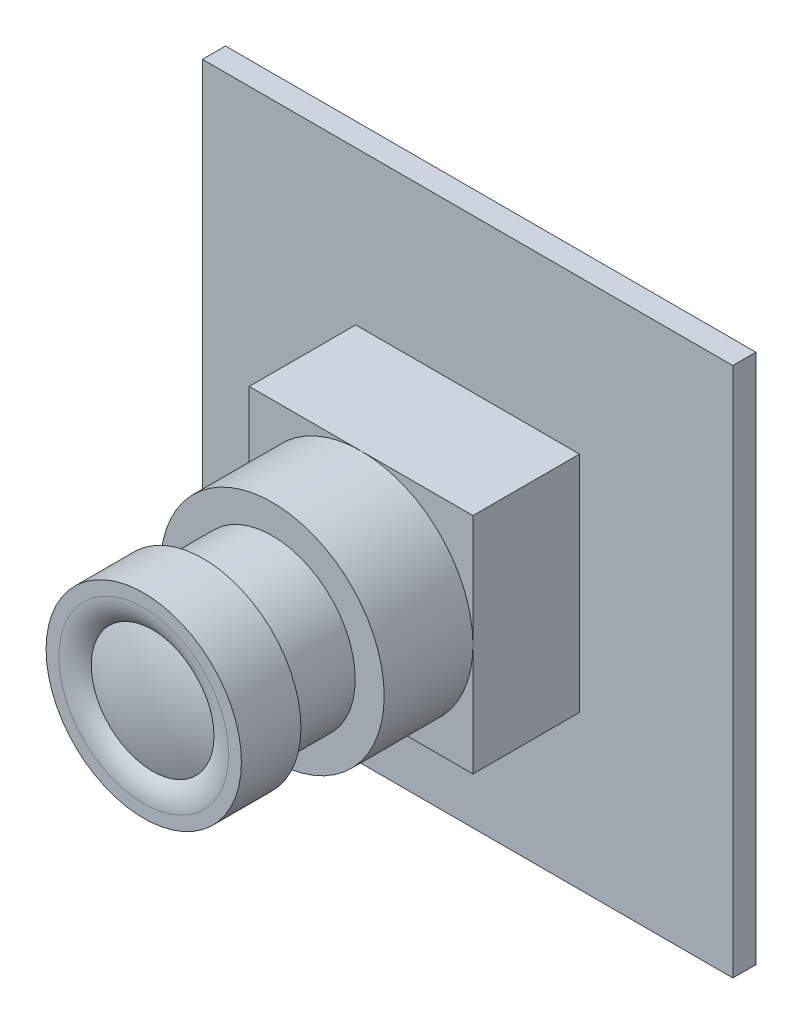
SolidWorks part; units mm, degrees
ref_plane "Front Plane" through (0, 0, 0) normal (0, 0, 1) x (1, 0, 0)
ref_plane "Top Plane" through (0, 0, 0) normal (0, 1, 0) x (1, 0, 0)
ref_plane "Right Plane" through (0, 0, 0) normal (1, 0, 0) x (0, 0, -1)
sketch "Sketch1" plane through (0, 0, 0) normal (0, 0, 1) x (1, 0, 0)
  line L1 (0, 37.9349) -> (37.9349, 37.9349)
  line L2 (0, 37.9349) -> (0, 0)
  line L3 (0, 0) -> (37.9349, 0)
  line L4 (37.9349, 37.9349) -> (37.9349, 0)
  dimension "D1" = 37.9349
extrude "Boss-Extrude1" add sketch "Sketch1" along normal blind 1.651
sketch "Sketch2" plane through (0, 0, 1.651) normal (0, 0, 1) x (1, 0, 0)
  line L0 (37.9349, 18.9675) -> (26.9685, 18.9675) construction
  line L1 (10.9665, 26.9685) -> (26.9684, 26.9685)
  line L2 (10.9665, 26.9685) -> (10.9665, 10.9665)
  line L3 (10.9665, 10.9665) -> (26.9685, 10.9665)
  line L4 (26.9684, 26.9685) -> (26.9685, 10.9665)
  line L5 (0, 0) -> (37.9349, 0) construction
  line L6 (37.9349, 0) -> (37.9349, 37.9349) construction
  line L7 (18.9674, 37.9349) -> (18.9675, 26.9685) construction
  line L10 (37.9349, 37.9349) -> (0, 37.9349) construction
  dimension "D1" = 16.002
extrude "Boss-Extrude2" add sketch "Sketch2" along normal blind 7.62
sketch "Sketch3" plane through (0, 0, 9.271) normal (0, 0, 1) x (1, 0, 0)
  line L1 (26.9684, 26.9685) -> (10.9665, 26.9685) construction
  line L2 (26.9685, 10.9665) -> (26.9684, 26.9685) construction
  line L3 (10.9665, 26.9685) -> (10.9665, 10.9665) construction
  line L4 (10.9665, 10.9665) -> (26.9685, 10.9665) construction
  circle A0 centre (18.9675, 18.9675) radius 8.001
extrude "Boss-Extrude3" add sketch "Sketch3" along normal blind 6.35
sketch "Sketch4" plane through (0, 0, 15.621) normal (0, 0, 1) x (1, 0, 0)
  circle A0 centre (18.9675, 18.9675) radius 5.9309
  circle A1 centre (18.9675, 18.9675) radius 8.001 construction
  dimension "D1" = 11.8618
extrude "Boss-Extrude4" add sketch "Sketch4" along normal blind 4.9403
sketch "Sketch5" plane through (0, 0, 20.5613) normal (0, 0, 1) x (1, 0, 0)
  circle A0 centre (18.9675, 18.9675) radius 6.985
  circle A1 centre (18.9675, 18.9675) radius 5.9309 construction
  dimension "D1" = 13.97
extrude "Boss-Extrude5" add sketch "Sketch5" along normal blind 4.2545
sketch "Sketch6" plane through (0, 0, 24.8158) normal (0, 0, 1) x (1, 0, 0)
  circle A0 centre (18.9675, 18.9675) radius 4.3878
  circle A1 centre (18.9675, 18.9675) radius 6.985 construction
  dimension "D1" = 8.7757
extrude "Cut-Extrude1" cut sketch "Sketch6" against normal blind 0.635
fillet "Fillet2" radius 2.54 1 edges at (23.3553, 18.9675, 24.8158)
dome "Dome1" faces to dome 1 distance 0.762 reverse direction no elliptical dome no face at (23.3553, 18.9675, 24.1808) parameters "D1"=0.762
sketch "Sketch9" plane through (0, 0, 1.651) normal (0, 0, 1) x (1, 0, 0)
  line L0 (32.8168, 32.8168) -> (37.9349, 32.8168) construction
  line L1 (0, 0) -> (37.9349, 0) construction
  line L2 (37.9349, 0) -> (37.9349, 37.9349) construction
  line L3 (32.8168, 37.9349) -> (32.8168, 32.8168) construction
  line L4 (0, 37.9349) -> (0, 0) construction
  line L5 (37.9349, 37.9349) -> (0, 37.9349) construction
  line L6 (5.1181, 37.9349) -> (5.1181, 32.8168) construction
  line L7 (0, 32.8168) -> (5.1181, 32.8168) construction
  line L8 (5.1181, 0) -> (5.1181, 5.1181) construction
  line L9 (0, 5.1181) -> (5.1181, 5.1181) construction
  line L10 (37.9349, 5.1181) -> (32.8168, 5.1181) construction
  line L11 (32.8168, 0) -> (32.8168, 5.1181) construction
  line L12 (18.9674, 37.9349) -> (18.9674, 36.1569) construction
  line L13 (15.508, 36.1569) -> (22.4269, 36.1569)
  line L14 (22.4269, 35.0692) -> (23.5146, 35.0692) construction
  line L15 (15.508, 33.9815) -> (22.4269, 33.9815)
  line L16 (15.508, 35.0692) -> (22.4269, 35.0692) construction
  line L17 (18.9674, 33.9815) -> (18.9675, 26.9685) construction
  line L18 (26.9684, 26.9685) -> (10.9665, 26.9685) construction
  line L19 (14.4203, 35.0692) -> (15.508, 35.0692) construction
  line L20 (15.375, 3.9534) -> (22.5599, 3.9534)
  line L21 (22.4269, 2.8739) -> (23.5146, 2.8739) construction
  line L22 (15.375, 1.7943) -> (22.5599, 1.7943)
  line L23 (15.508, 2.8739) -> (22.4269, 2.8739) construction
  line L24 (14.4203, 2.8739) -> (15.508, 2.8739) construction
  line L25 (33.9815, 22.5599) -> (33.9815, 15.375)
  line L26 (18.9675, 10.9665) -> (18.9675, 3.9534) construction
  line L27 (18.9675, 3.9534) -> (18.9674, 1.7943) construction
  line L28 (36.1394, 22.5599) -> (36.1394, 15.375)
  line L29 (10.9665, 10.9665) -> (26.9685, 10.9665) construction
  line L30 (18.9674, 1.7943) -> (18.9674, 0) construction
  line L31 (18.9674, 36.1569) -> (18.9674, 33.9815) construction
  line L32 (33.9815, 15.375) -> (36.1394, 15.375) construction
  line L33 (35.0604, 22.4269) -> (35.0604, 15.508) construction
  line L34 (35.0604, 23.5141) -> (35.0604, 22.4269) construction
  line L35 (35.0604, 15.508) -> (35.0604, 14.4209) construction
  line L36 (26.9685, 18.9675) -> (33.9815, 18.9675) construction
  line L37 (26.9685, 10.9665) -> (26.9684, 26.9685) construction
  line L38 (1.7955, 22.5599) -> (1.7955, 15.375)
  line L39 (3.9534, 22.5599) -> (3.9534, 15.375)
  line L40 (1.7955, 15.375) -> (3.9534, 15.375) construction
  line L41 (2.8745, 22.4269) -> (2.8745, 15.508) construction
  line L42 (2.8745, 23.5141) -> (2.8745, 22.4269) construction
  line L43 (2.8745, 15.508) -> (2.8745, 14.4209) construction
  line L44 (3.9534, 18.9675) -> (10.9665, 18.9675) construction
  line L45 (10.9665, 26.9685) -> (10.9665, 10.9665) construction
  line L46 (0, 18.9674) -> (1.7955, 18.9675) construction
  circle A0 centre (32.8168, 32.8168) radius 1.1176
  circle A1 centre (5.1181, 32.8168) radius 1.1176
  circle A2 centre (5.1181, 5.1181) radius 1.1176
  circle A3 centre (32.8168, 5.1181) radius 1.1176
  arc A4 (22.4269, 36.1569) -> (22.4269, 33.9815) centre (22.4269, 35.0692) cw
  arc A5 (15.508, 36.1569) -> (15.508, 33.9815) centre (15.508, 35.0692) ccw
  arc A6 (22.5599, 3.9534) -> (22.5599, 1.7943) centre (22.4269, 2.8739) cw
  arc A7 (15.375, 3.9534) -> (15.375, 1.7943) centre (15.508, 2.8739) ccw
  arc A8 (33.9815, 22.5599) -> (36.1394, 22.5599) centre (35.0604, 22.4269) cw
  arc A9 (33.9815, 15.375) -> (36.1394, 15.375) centre (35.0604, 15.508) ccw
  arc A10 (1.7955, 22.5599) -> (3.9534, 22.5599) centre (2.8745, 22.4269) cw
  arc A11 (1.7955, 15.375) -> (3.9534, 15.375) centre (2.8745, 15.508) ccw
  dimension "D1" = 2.2352
  dimension "D3" = 1.0877
  dimension "D2" = 5.1181
  dimension "D4" = 1.778
  dimension "D5" = 7.013
  dimension "D6" = 6.919
  dimension "D7" = 1.0877
  dimension "D8" = 6.919
  dimension "D9" = 7.013
  dimension "D10" = 2.1591
  dimension "D11" = 1.7943
  dimension "D12" = 6.919
  dimension "D13" = 1.0871
  dimension "D14" = 7.013
  dimension "D15" = 6.919
  dimension "D16" = 1.0871
  dimension "D17" = 7.013
  dimension "D18" = 1.7955
